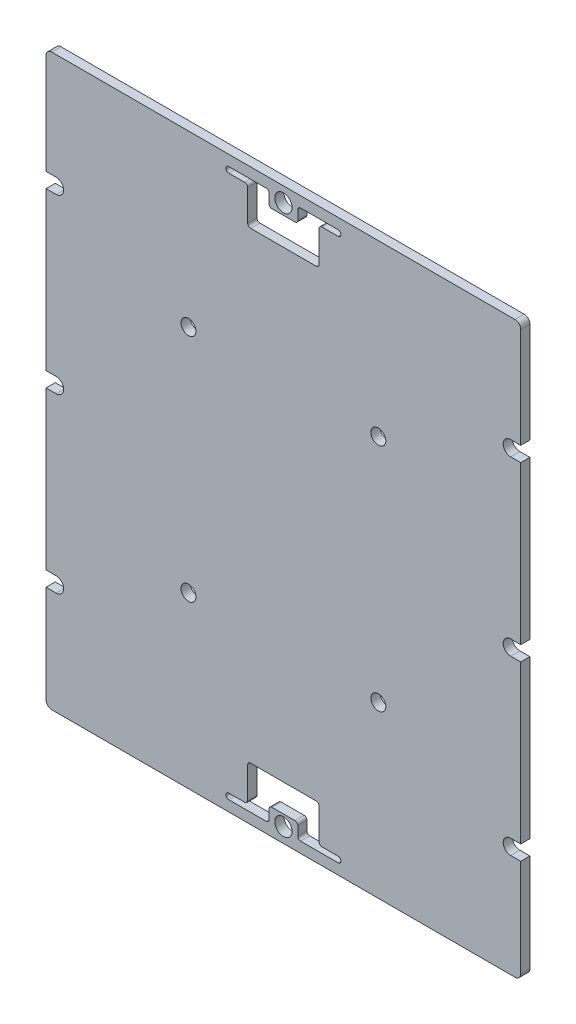
SolidWorks part; units mm, degrees
material "FR4_stuffedProtoboard"
ref_plane "Front Plane" through (0, 0, 0) normal (0, 0, 1) x (1, 0, 0)
ref_plane "Top Plane" through (0, 0, 0) normal (0, 1, 0) x (1, 0, 0)
ref_plane "Right Plane" through (0, 0, 0) normal (1, 0, 0) x (0, 0, -1)
sketch "Sketch2" plane through (0, 0, 0) normal (0, 0, 1) x (1, 0, 0)
  line L0 (39, 49.75) -> (-39, 49.75) construction
  line L1 (-41.5, 49.75) -> (41.5, 49.75) construction
  line L2 (-41.5, 49.75) -> (-41.5, -49.75) construction
  line L3 (-41.5, -49.75) -> (41.5, -49.75) construction
  line L4 (41.5, 49.75) -> (41.5, -49.75) construction
  line L5 (-41.5, 49.75) -> (41.5, -49.75) construction
  line L6 (-41.5, -49.75) -> (41.5, 49.75) construction
  line L7 (41.5, 52.25) -> (41.5, 40.15) construction
  line L8 (-41.5, 49.75) -> (41.5, 49.75) construction
  line L9 (41.5, 49.75) -> (41.5, -49.75) construction
  line L10 (-41.5, -49.75) -> (41.5, -49.75) construction
  line L11 (-41.5, 49.75) -> (-41.5, -49.75) construction
  line L12 (-37, -31.85) -> (37, -31.85) construction
  line L13 (-37, -30.25) -> (37, -30.25) construction
  line L14 (-37, -21.85) -> (37, -21.85) construction
  line L15 (-37, -20.25) -> (37, -20.25) construction
  line L16 (-37, -11.85) -> (37, -11.85) construction
  line L17 (-37, -10.25) -> (37, -10.25) construction
  line L18 (-37, -1.85) -> (37, -1.85) construction
  line L19 (-37, -0.25) -> (37, -0.25) construction
  line L20 (-37, 8.15) -> (37, 8.15) construction
  line L21 (-37, 9.75) -> (37, 9.75) construction
  line L22 (-37, 18.15) -> (37, 18.15) construction
  line L23 (-37, 19.75) -> (37, 19.75) construction
  line L24 (-37, 28.15) -> (37, 28.15) construction
  line L25 (-37, 29.75) -> (37, 29.75) construction
  line L26 (-37, 38.15) -> (37, 38.15) construction
  line L27 (-37, 39.75) -> (37, 39.75) construction
  line L28 (-37, -31.85) -> (37, -31.85) construction
  line L29 (-37, -30.25) -> (37, -30.25) construction
  line L30 (-37, -21.85) -> (37, -21.85) construction
  line L31 (-37, -20.25) -> (37, -20.25) construction
  line L32 (-37, -11.85) -> (37, -11.85) construction
  line L33 (-37, -10.25) -> (37, -10.25) construction
  line L34 (-37, -1.85) -> (37, -1.85) construction
  line L35 (-37, -0.25) -> (37, -0.25) construction
  line L36 (-37, 8.15) -> (37, 8.15) construction
  line L37 (-37, 9.75) -> (37, 9.75) construction
  line L38 (-37, 18.15) -> (37, 18.15) construction
  line L39 (-37, 19.75) -> (37, 19.75) construction
  line L40 (-37, 28.15) -> (37, 28.15) construction
  line L41 (-37, 29.75) -> (37, 29.75) construction
  line L42 (-37, 38.15) -> (37, 38.15) construction
  line L43 (-37, 39.75) -> (37, 39.75) construction
  line L44 (-37, -40.25) -> (37, -40.25) construction
  line L45 (-37, -41.85) -> (37, -41.85) construction
  line L46 (-41.5, 52.25) -> (-41.5, 40.15) construction
  line L47 (39, -49.75) -> (-39, -49.75) construction
  line L48 (41.5, -31.7) -> (41.5, -52.25) construction
  line L49 (-41.25, 49.5) -> (41.25, 49.5)
  line L50 (41.25, 49.5) -> (41.25, -49.5)
  line L51 (-41.25, -49.5) -> (41.25, -49.5)
  line L52 (-41.25, 49.5) -> (-41.25, -49.5)
  circle A0 centre (0, 46.95) radius 1.5 construction
  circle A1 centre (0, 46.95) radius 0.8 construction
  circle A2 centre (0, 46.95) radius 1.5 construction
  circle A3 centre (0, 46.95) radius 0.8
  circle A4 centre (-39.5, -30.25) radius 0.8 construction
  circle A5 centre (-39.5, -0.25) radius 0.8 construction
  circle A6 centre (-39.5, 29.75) radius 0.8 construction
  circle A7 centre (-39.5, -30.25) radius 0.8
  circle A8 centre (-39.5, -0.25) radius 0.8
  circle A9 centre (-39.5, 29.75) radius 0.8
  circle A10 centre (39.5, -30.25) radius 0.8 construction
  circle A11 centre (39.5, -0.25) radius 0.8 construction
  circle A12 centre (39.5, 29.75) radius 0.8 construction
  circle A13 centre (39.5, -30.25) radius 0.8
  circle A14 centre (39.5, -0.25) radius 0.8
  circle A15 centre (39.5, 29.75) radius 0.8
  circle A16 centre (0, -46.95) radius 0.8 construction
  circle A17 centre (0, -46.95) radius 0.8
  circle A18 centre (0, -46.95) radius 1.5 construction
  circle A19 centre (0, -46.95) radius 1.5
  circle A20 centre (-16.5, 20) radius 1.75 construction
  circle A21 centre (-16.5, 20) radius 0.8 construction
  circle A22 centre (-16.5, 20) radius 1.75 construction
  circle A23 centre (-16.5, 20) radius 0.8
  circle A24 centre (16.5, 20) radius 1.75 construction
  circle A25 centre (16.5, 20) radius 0.8 construction
  circle A26 centre (16.5, 20) radius 1.75 construction
  circle A27 centre (16.5, 20) radius 0.8
  circle A28 centre (16.5, -20) radius 1.75 construction
  circle A29 centre (-16.5, -20) radius 1.75 construction
  circle A30 centre (16.5, -20) radius 1.75 construction
  circle A31 centre (-16.5, -20) radius 1.75 construction
  circle A32 centre (-16.5, -20) radius 0.8 construction
  circle A33 centre (-16.5, -20) radius 0.8
  circle A34 centre (16.5, -20) radius 0.8 construction
  circle A35 centre (16.5, -20) radius 0.8
  point P0 (0, 0)
  point P74 (0, -40.25)
  point P75 (0, -31.85)
  point P76 (0, -41.85)
  dimension "D2" = 10
  dimension "D3" = 1.6
  dimension "D1" = 0.25
extrude "pcb extrude" add sketch "Sketch2" along normal mid plane 1.6 contours L4 L1 L2 L3 A2 | A2 A3 | L2 L1 L4 L3 region at (0, 0.0296, 0)
sketch "connector locations" plane through (0, 0, 0.8) normal (0, 0, 1) x (1, 0, 0)
  line L0 (34.5, 45.75) -> (4.5, 45.75) construction
  line L1 (-2.5, 44.75) -> (2.5, 44.75) construction
  line L2 (-4.5, 45.75) -> (-34.5, 45.75) construction
  line L3 (34.5, 45.75) -> (4.5, 45.75)
  line L4 (-2.5, 44.75) -> (2.5, 44.75)
  line L5 (-4.5, 45.75) -> (-34.5, 45.75)
  line L6 (-37, 43.25) -> (-37, -43.25) construction
  line L7 (-37, 43.25) -> (-37, -43.25)
  line L8 (37, -43.25) -> (37, 43.25) construction
  line L9 (37, -43.25) -> (37, 43.25)
  line L10 (4.5, -45.75) -> (34.5, -45.75) construction
  line L11 (4.5, -45.75) -> (34.5, -45.75)
  line L12 (-34.5, -45.75) -> (-4.5, -45.75) construction
  line L13 (-2.5, -44.75) -> (2.5, -44.75) construction
  line L14 (-34.5, -45.75) -> (-4.5, -45.75)
  line L15 (-2.5, -44.75) -> (2.5, -44.75)
  line L16 (-37, 39.75) -> (37, 39.75) construction
  line L17 (-33.9182, 41.909) -> (-9.2802, 41.909)
  line L18 (-33.9182, 41.909) -> (-33.9182, 43.306)
  line L19 (-33.9182, 43.306) -> (-9.2802, 43.306)
  line L20 (-9.2802, 41.909) -> (-9.2802, 43.306)
  line L21 (-33.9182, 41.909) -> (-9.2802, 43.306) construction
  line L22 (-33.9182, 43.306) -> (-9.2802, 41.909) construction
  line L23 (-33.9182, 33.306) -> (-22.0818, 33.306)
  line L24 (-33.9182, 33.306) -> (-33.9182, 31.909)
  line L25 (-33.9182, 31.909) -> (-22.0818, 31.909)
  line L26 (-22.0818, 33.306) -> (-22.0818, 31.909)
  line L27 (-33.9182, 33.306) -> (-22.0818, 31.909) construction
  line L28 (-33.9182, 31.909) -> (-22.0818, 33.306) construction
  line L29 (-12.319, 33.306) -> (12.319, 33.306)
  line L30 (-12.319, 33.306) -> (-12.319, 31.909)
  line L31 (-12.319, 31.909) -> (12.319, 31.909)
  line L32 (12.319, 33.306) -> (12.319, 31.909)
  line L33 (-12.319, 33.306) -> (12.319, 31.909) construction
  line L34 (-12.319, 31.909) -> (12.319, 33.306) construction
  line L35 (-33.9182, 23.306) -> (-22.0818, 23.306)
  line L36 (-33.9182, 23.306) -> (-33.9182, 21.909)
  line L37 (-33.9182, 21.909) -> (-22.0818, 21.909)
  line L38 (-33.9182, 23.306) -> (-22.0818, 21.909) construction
  line L39 (-33.9182, 21.909) -> (-22.0818, 23.306) construction
  line L40 (-22.0818, 23.306) -> (-22.0818, 21.909)
  line L41 (-12.319, 23.306) -> (-12.319, 21.909)
  line L42 (-12.319, 23.306) -> (12.319, 23.306)
  line L43 (-12.319, 21.909) -> (12.319, 21.909)
  line L44 (-12.319, 23.306) -> (12.319, 21.909) construction
  line L45 (-12.319, 21.909) -> (12.319, 23.306) construction
  line L46 (12.319, 23.306) -> (12.319, 21.909)
  line L47 (-33.9182, 13.306) -> (-22.0818, 13.306)
  line L48 (-33.9182, 13.306) -> (-33.9182, 11.909)
  line L49 (-33.9182, 11.909) -> (-22.0818, 11.909)
  line L50 (-33.9182, 13.306) -> (-22.0818, 11.909) construction
  line L51 (-33.9182, 11.909) -> (-22.0818, 13.306) construction
  line L52 (-22.0818, 13.306) -> (-22.0818, 11.909)
  line L53 (-12.319, 13.306) -> (-12.319, 11.909)
  line L54 (-12.319, 13.306) -> (12.319, 13.306)
  line L55 (-12.319, 11.909) -> (12.319, 11.909)
  line L56 (-12.319, 13.306) -> (12.319, 11.909) construction
  line L57 (-12.319, 11.909) -> (12.319, 13.306) construction
  line L58 (12.319, 13.306) -> (12.319, 11.909)
  line L59 (-33.9182, 3.306) -> (-22.0818, 3.306)
  line L60 (-33.9182, 3.306) -> (-33.9182, 1.909)
  line L61 (-33.9182, 1.909) -> (-22.0818, 1.909)
  line L62 (-33.9182, 3.306) -> (-22.0818, 1.909) construction
  line L63 (-33.9182, 1.909) -> (-22.0818, 3.306) construction
  line L64 (-22.0818, 3.306) -> (-22.0818, 1.909)
  line L65 (-12.319, 3.306) -> (-12.319, 1.909)
  line L66 (-12.319, 3.306) -> (12.319, 3.306)
  line L67 (-12.319, 1.909) -> (12.319, 1.909)
  line L68 (-12.319, 3.306) -> (12.319, 1.909) construction
  line L69 (-12.319, 1.909) -> (12.319, 3.306) construction
  line L70 (12.319, 3.306) -> (12.319, 1.909)
  line L71 (-33.9182, -6.694) -> (-22.0818, -6.694)
  line L72 (-33.9182, -6.694) -> (-33.9182, -8.091)
  line L73 (-33.9182, -8.091) -> (-22.0818, -8.091)
  line L74 (-33.9182, -6.694) -> (-22.0818, -8.091) construction
  line L75 (-33.9182, -8.091) -> (-22.0818, -6.694) construction
  line L76 (-22.0818, -6.694) -> (-22.0818, -8.091)
  line L77 (-12.319, -6.694) -> (-12.319, -8.091)
  line L78 (-12.319, -6.694) -> (12.319, -6.694)
  line L79 (-12.319, -8.091) -> (12.319, -8.091)
  line L80 (-12.319, -6.694) -> (12.319, -8.091) construction
  line L81 (-12.319, -8.091) -> (12.319, -6.694) construction
  line L82 (12.319, -6.694) -> (12.319, -8.091)
  line L83 (-33.9182, -16.694) -> (-22.0818, -16.694)
  line L84 (-33.9182, -16.694) -> (-33.9182, -18.091)
  line L85 (-33.9182, -18.091) -> (-22.0818, -18.091)
  line L86 (-33.9182, -16.694) -> (-22.0818, -18.091) construction
  line L87 (-33.9182, -18.091) -> (-22.0818, -16.694) construction
  line L88 (-22.0818, -16.694) -> (-22.0818, -18.091)
  line L89 (-12.319, -16.694) -> (-12.319, -18.091)
  line L90 (-12.319, -16.694) -> (12.319, -16.694)
  line L91 (-12.319, -18.091) -> (12.319, -18.091)
  line L92 (-12.319, -16.694) -> (12.319, -18.091) construction
  line L93 (-12.319, -18.091) -> (12.319, -16.694) construction
  line L94 (12.319, -16.694) -> (12.319, -18.091)
  line L95 (-33.9182, -26.694) -> (-22.0818, -26.694)
  line L96 (-33.9182, -26.694) -> (-33.9182, -28.091)
  line L97 (-33.9182, -28.091) -> (-22.0818, -28.091)
  line L98 (-33.9182, -26.694) -> (-22.0818, -28.091) construction
  line L99 (-33.9182, -28.091) -> (-22.0818, -26.694) construction
  line L100 (-22.0818, -26.694) -> (-22.0818, -28.091)
  line L101 (-12.319, -26.694) -> (-12.319, -28.091)
  line L102 (-12.319, -26.694) -> (12.319, -26.694)
  line L103 (-12.319, -28.091) -> (12.319, -28.091)
  line L104 (-12.319, -26.694) -> (12.319, -28.091) construction
  line L105 (-12.319, -28.091) -> (12.319, -26.694) construction
  line L106 (12.319, -26.694) -> (12.319, -28.091)
  line L107 (-33.9182, -36.694) -> (-22.0818, -36.694)
  line L108 (-33.9182, -36.694) -> (-33.9182, -38.091)
  line L109 (-33.9182, -38.091) -> (-22.0818, -38.091)
  line L110 (-33.9182, -36.694) -> (-22.0818, -38.091) construction
  line L111 (-33.9182, -38.091) -> (-22.0818, -36.694) construction
  line L112 (-22.0818, -36.694) -> (-22.0818, -38.091)
  line L113 (-12.319, -36.694) -> (-12.319, -38.091)
  line L114 (-12.319, -36.694) -> (12.319, -36.694)
  line L115 (-12.319, -38.091) -> (12.319, -38.091)
  line L116 (-12.319, -36.694) -> (12.319, -38.091) construction
  line L117 (-12.319, -38.091) -> (12.319, -36.694) construction
  line L118 (12.319, -36.694) -> (12.319, -38.091)
  line L119 (0, 32.6075) -> (0, 22.6075) construction
  line L120 (-37, 29.75) -> (37, 29.75) construction
  line L121 (32.92, 41.02) -> (35.08, 38.84) construction
  line L122 (32.92, 38.84) -> (35.08, 41.02) construction
  line L123 (26.92, 38.84) -> (29.08, 41.02) construction
  line L124 (26.92, 41.02) -> (29.08, 38.84) construction
  line L125 (20.92, 38.84) -> (23.08, 41.02) construction
  line L126 (20.92, 41.02) -> (23.08, 38.84) construction
  line L127 (26.92, 28.84) -> (29.08, 31.02) construction
  line L128 (26.92, 31.02) -> (29.08, 28.84) construction
  line L129 (20.92, 28.84) -> (23.08, 31.02) construction
  line L130 (20.92, 31.02) -> (23.08, 28.84) construction
  line L131 (26.92, 18.84) -> (29.08, 21.02) construction
  line L132 (26.92, 21.02) -> (29.08, 18.84) construction
  line L133 (20.92, 18.84) -> (23.08, 21.02) construction
  line L134 (20.92, 21.02) -> (23.08, 18.84) construction
  line L135 (26.92, 8.84) -> (29.08, 11.02) construction
  line L136 (26.92, 11.02) -> (29.08, 8.84) construction
  line L137 (20.92, 8.84) -> (23.08, 11.02) construction
  line L138 (20.92, 11.02) -> (23.08, 8.84) construction
  line L139 (26.92, -1.16) -> (29.08, 1.02) construction
  line L140 (26.92, 1.02) -> (29.08, -1.16) construction
  line L141 (20.92, -1.16) -> (23.08, 1.02) construction
  line L142 (20.92, 1.02) -> (23.08, -1.16) construction
  line L143 (26.92, -11.16) -> (29.08, -8.98) construction
  line L144 (26.92, -8.98) -> (29.08, -11.16) construction
  line L145 (20.92, -11.16) -> (23.08, -8.98) construction
  line L146 (20.92, -8.98) -> (23.08, -11.16) construction
  line L147 (26.92, -21.16) -> (29.08, -18.98) construction
  line L148 (26.92, -18.98) -> (29.08, -21.16) construction
  line L149 (20.92, -21.16) -> (23.08, -18.98) construction
  line L150 (20.92, -18.98) -> (23.08, -21.16) construction
  line L151 (26.92, -31.16) -> (29.08, -28.98) construction
  line L152 (26.92, -28.98) -> (29.08, -31.16) construction
  line L153 (20.92, -31.16) -> (23.08, -28.98) construction
  line L154 (20.92, -28.98) -> (23.08, -31.16) construction
  line L155 (26.92, -41.16) -> (29.08, -38.98) construction
  line L156 (26.92, -38.98) -> (29.08, -41.16) construction
  line L157 (20.92, -41.16) -> (23.08, -38.98) construction
  line L158 (20.92, -38.98) -> (23.08, -41.16) construction
  line L159 (32.92, 28.84) -> (35.08, 31.02) construction
  line L160 (32.92, 31.02) -> (35.08, 28.84) construction
  line L161 (32.92, 18.84) -> (35.08, 21.02) construction
  line L162 (32.92, 21.02) -> (35.08, 18.84) construction
  line L163 (32.92, 8.84) -> (35.08, 11.02) construction
  line L164 (32.92, 11.02) -> (35.08, 8.84) construction
  line L165 (32.92, -1.16) -> (35.08, 1.02) construction
  line L166 (32.92, 1.02) -> (35.08, -1.16) construction
  line L167 (32.92, -11.16) -> (35.08, -8.98) construction
  line L168 (32.92, -8.98) -> (35.08, -11.16) construction
  line L169 (32.92, -21.16) -> (35.08, -18.98) construction
  line L170 (32.92, -18.98) -> (35.08, -21.16) construction
  line L171 (32.92, -31.16) -> (35.08, -28.98) construction
  line L172 (32.92, -28.98) -> (35.08, -31.16) construction
  line L173 (32.92, -41.16) -> (35.08, -38.98) construction
  line L174 (32.92, -38.98) -> (35.08, -41.16) construction
  line L175 (34, 39.93) -> (28, 39.93) construction
  line L176 (34, 39.93) -> (34, 29.93) construction
  arc A0 (4.5, 45.75) -> (2.5, 44.75) centre (4.5, 43.25) ccw construction
  arc A1 (-2.5, 44.75) -> (-4.5, 45.75) centre (-4.5, 43.25) ccw construction
  arc A2 (-34.5, 45.75) -> (-37, 43.25) centre (-34.5, 43.25) ccw construction
  arc A3 (4.5, 45.75) -> (2.5, 44.75) centre (4.5, 43.25) ccw
  arc A4 (-2.5, 44.75) -> (-4.5, 45.75) centre (-4.5, 43.25) ccw
  arc A5 (-34.5, 45.75) -> (-37, 43.25) centre (-34.5, 43.25) ccw
  arc A6 (37, 43.25) -> (34.5, 45.75) centre (34.5, 43.25) ccw construction
  arc A7 (37, 43.25) -> (34.5, 45.75) centre (34.5, 43.25) ccw
  arc A8 (34.5, -45.75) -> (37, -43.25) centre (34.5, -43.25) ccw construction
  arc A9 (34.5, -45.75) -> (37, -43.25) centre (34.5, -43.25) ccw
  arc A10 (-37, -43.25) -> (-34.5, -45.75) centre (-34.5, -43.25) ccw construction
  arc A11 (-4.5, -45.75) -> (-2.5, -44.75) centre (-4.5, -43.25) ccw construction
  arc A12 (2.5, -44.75) -> (4.5, -45.75) centre (4.5, -43.25) ccw construction
  arc A13 (-37, -43.25) -> (-34.5, -45.75) centre (-34.5, -43.25) ccw
  arc A14 (-4.5, -45.75) -> (-2.5, -44.75) centre (-4.5, -43.25) ccw
  arc A15 (2.5, -44.75) -> (4.5, -45.75) centre (4.5, -43.25) ccw
  circle A16 centre (-21.5992, 42.6075) radius 0.5
  circle A17 centre (0, 32.6075) radius 0.5
  circle A18 centre (-28, 32.6075) radius 0.5
  circle A19 centre (-28, 22.6075) radius 0.5
  circle A20 centre (0, 22.6075) radius 0.5
  circle A21 centre (-28, 12.6075) radius 0.5
  circle A22 centre (0, 12.6075) radius 0.5
  circle A23 centre (-28, 2.6075) radius 0.5
  circle A24 centre (0, 2.6075) radius 0.5
  circle A25 centre (-28, -7.3925) radius 0.5
  circle A26 centre (0, -7.3925) radius 0.5
  circle A27 centre (-28, -17.3925) radius 0.5
  circle A28 centre (0, -17.3925) radius 0.5
  circle A29 centre (-28, -27.3925) radius 0.5
  circle A30 centre (0, -27.3925) radius 0.5
  circle A31 centre (-28, -37.3925) radius 0.5
  circle A32 centre (0, -37.3925) radius 0.5
  circle A33 centre (35.08, 41.02) radius 0.32
  circle A34 centre (32.92, 38.84) radius 0.32
  circle A35 centre (35.08, 38.84) radius 0.32
  circle A36 centre (32.92, 41.02) radius 0.32
  circle A37 centre (26.92, 41.02) radius 0.32
  circle A38 centre (29.08, 41.02) radius 0.32
  circle A39 centre (26.92, 38.84) radius 0.32
  circle A40 centre (29.08, 38.84) radius 0.32
  circle A41 centre (20.92, 41.02) radius 0.32
  circle A42 centre (23.08, 41.02) radius 0.32
  circle A43 centre (20.92, 38.84) radius 0.32
  circle A44 centre (23.08, 38.84) radius 0.32
  circle A45 centre (26.92, 31.02) radius 0.32
  circle A46 centre (29.08, 31.02) radius 0.32
  circle A47 centre (26.92, 28.84) radius 0.32
  circle A48 centre (29.08, 28.84) radius 0.32
  circle A49 centre (20.92, 31.02) radius 0.32
  circle A50 centre (23.08, 31.02) radius 0.32
  circle A51 centre (20.92, 28.84) radius 0.32
  circle A52 centre (23.08, 28.84) radius 0.32
  circle A53 centre (26.92, 21.02) radius 0.32
  circle A54 centre (29.08, 21.02) radius 0.32
  circle A55 centre (26.92, 18.84) radius 0.32
  circle A56 centre (29.08, 18.84) radius 0.32
  circle A57 centre (20.92, 21.02) radius 0.32
  circle A58 centre (23.08, 21.02) radius 0.32
  circle A59 centre (20.92, 18.84) radius 0.32
  circle A60 centre (23.08, 18.84) radius 0.32
  circle A61 centre (26.92, 11.02) radius 0.32
  circle A62 centre (29.08, 11.02) radius 0.32
  circle A63 centre (26.92, 8.84) radius 0.32
  circle A64 centre (29.08, 8.84) radius 0.32
  circle A65 centre (20.92, 11.02) radius 0.32
  circle A66 centre (23.08, 11.02) radius 0.32
  circle A67 centre (20.92, 8.84) radius 0.32
  circle A68 centre (23.08, 8.84) radius 0.32
  circle A69 centre (26.92, 1.02) radius 0.32
  circle A70 centre (29.08, 1.02) radius 0.32
  circle A71 centre (26.92, -1.16) radius 0.32
  circle A72 centre (29.08, -1.16) radius 0.32
  circle A73 centre (20.92, 1.02) radius 0.32
  circle A74 centre (23.08, 1.02) radius 0.32
  circle A75 centre (20.92, -1.16) radius 0.32
  circle A76 centre (23.08, -1.16) radius 0.32
  circle A77 centre (26.92, -8.98) radius 0.32
  circle A78 centre (29.08, -8.98) radius 0.32
  circle A79 centre (26.92, -11.16) radius 0.32
  circle A80 centre (29.08, -11.16) radius 0.32
  circle A81 centre (20.92, -8.98) radius 0.32
  circle A82 centre (23.08, -8.98) radius 0.32
  circle A83 centre (20.92, -11.16) radius 0.32
  circle A84 centre (23.08, -11.16) radius 0.32
  circle A85 centre (26.92, -18.98) radius 0.32
  circle A86 centre (29.08, -18.98) radius 0.32
  circle A87 centre (26.92, -21.16) radius 0.32
  circle A88 centre (29.08, -21.16) radius 0.32
  circle A89 centre (20.92, -18.98) radius 0.32
  circle A90 centre (23.08, -18.98) radius 0.32
  circle A91 centre (20.92, -21.16) radius 0.32
  circle A92 centre (23.08, -21.16) radius 0.32
  circle A93 centre (26.92, -28.98) radius 0.32
  circle A94 centre (29.08, -28.98) radius 0.32
  circle A95 centre (26.92, -31.16) radius 0.32
  circle A96 centre (29.08, -31.16) radius 0.32
  circle A97 centre (20.92, -28.98) radius 0.32
  circle A98 centre (23.08, -28.98) radius 0.32
  circle A99 centre (20.92, -31.16) radius 0.32
  circle A100 centre (23.08, -31.16) radius 0.32
  circle A101 centre (26.92, -38.98) radius 0.32
  circle A102 centre (29.08, -38.98) radius 0.32
  circle A103 centre (26.92, -41.16) radius 0.32
  circle A104 centre (29.08, -41.16) radius 0.32
  circle A105 centre (20.92, -38.98) radius 0.32
  circle A106 centre (23.08, -38.98) radius 0.32
  circle A107 centre (20.92, -41.16) radius 0.32
  circle A108 centre (23.08, -41.16) radius 0.32
  circle A109 centre (32.92, 31.02) radius 0.32
  circle A110 centre (35.08, 31.02) radius 0.32
  circle A111 centre (32.92, 28.84) radius 0.32
  circle A112 centre (35.08, 28.84) radius 0.32
  circle A113 centre (32.92, 21.02) radius 0.32
  circle A114 centre (35.08, 21.02) radius 0.32
  circle A115 centre (32.92, 18.84) radius 0.32
  circle A116 centre (35.08, 18.84) radius 0.32
  circle A117 centre (32.92, 11.02) radius 0.32
  circle A118 centre (35.08, 11.02) radius 0.32
  circle A119 centre (32.92, 8.84) radius 0.32
  circle A120 centre (35.08, 8.84) radius 0.32
  circle A121 centre (32.92, 1.02) radius 0.32
  circle A122 centre (35.08, 1.02) radius 0.32
  circle A123 centre (32.92, -1.16) radius 0.32
  circle A124 centre (35.08, -1.16) radius 0.32
  circle A125 centre (32.92, -8.98) radius 0.32
  circle A126 centre (35.08, -8.98) radius 0.32
  circle A127 centre (32.92, -11.16) radius 0.32
  circle A128 centre (35.08, -11.16) radius 0.32
  circle A129 centre (32.92, -18.98) radius 0.32
  circle A130 centre (35.08, -18.98) radius 0.32
  circle A131 centre (32.92, -21.16) radius 0.32
  circle A132 centre (35.08, -21.16) radius 0.32
  circle A133 centre (32.92, -28.98) radius 0.32
  circle A134 centre (35.08, -28.98) radius 0.32
  circle A135 centre (32.92, -31.16) radius 0.32
  circle A136 centre (35.08, -31.16) radius 0.32
  circle A137 centre (32.92, -38.98) radius 0.32
  circle A138 centre (35.08, -38.98) radius 0.32
  circle A139 centre (32.92, -41.16) radius 0.32
  circle A140 centre (35.08, -41.16) radius 0.32
  point P18 (-21.5992, 42.6075)
  point P29 (-28, 32.6075)
  point P34 (0, 32.6075)
  point P50 (-28, 22.6075)
  point P55 (0, 22.6075)
  point P64 (-28, 12.6075)
  point P69 (0, 12.6075)
  point P78 (-28, 2.6075)
  point P83 (0, 2.6075)
  point P92 (-28, -7.3925)
  point P97 (0, -7.3925)
  point P106 (-28, -17.3925)
  point P111 (0, -17.3925)
  point P120 (-28, -27.3925)
  point P125 (0, -27.3925)
  point P134 (-28, -37.3925)
  point P139 (0, -37.3925)
  point P158 (0, 0)
  point P165 (34, 39.93)
  point P170 (28, 39.93)
  point P179 (22, 39.93)
  point P188 (28, 29.93)
  point P197 (22, 29.93)
  point P206 (28, 19.93)
  point P215 (22, 19.93)
  point P224 (28, 9.93)
  point P233 (22, 9.93)
  point P242 (28, -0.07)
  point P251 (22, -0.07)
  point P260 (28, -10.07)
  point P269 (22, -10.07)
  point P278 (28, -20.07)
  point P287 (22, -20.07)
  point P296 (28, -30.07)
  point P305 (22, -30.07)
  point P314 (28, -40.07)
  point P323 (22, -40.07)
  point P332 (34, 29.93)
  point P341 (34, 19.93)
  point P350 (34, 9.93)
  point P359 (34, -0.07)
  point P368 (34, -10.07)
  point P377 (34, -20.07)
  point P386 (34, -30.07)
  point P395 (34, -40.07)
  dimension "D4" = 1
  dimension "D5" = 11.8364
  dimension "D10" = 0.64
  dimension "D1" = 24.638
  dimension "D2" = 1.397
  dimension "D3" = 2.159
  dimension "D6" = 28
  dimension "D8" = 10
  dimension "D9" = 2.159
  dimension "D11" = 2.18
  dimension "D12" = 2.16
  dimension "D13" = 0.18
  dimension "D14" = 34
  dimension "D17" = 6
  dimension "D18" = 10
  dimension "D7" = 8
  dimension "D15" = 3
  dimension "D16" = 9
fillet "corner fillets" radius 1 4 edges at (41.25, -49.5, 0) (-41.25, -49.5, 0) (41.25, 49.5, 0) (-41.25, 49.5, 0)
sketch "Sketch4" plane through (0, 0, 0.8) normal (0, 0, 1) x (1, 0, 0)
  line L0 (0, 46.95) -> (0, 40.25) construction
  line L1 (6.2, 40.25) -> (-6.2, 40.25)
  line L2 (-6.2, 40.25) -> (-6.2, 46.65)
  line L3 (-6.2, 46.65) -> (-9.5, 46.65)
  line L4 (-4.5, 45.75) -> (-34.5, 45.75) construction
  line L5 (-9.5, 47.65) -> (-2.5, 47.65)
  line L6 (-2.5, 47.65) -> (-2.5, 45.05)
  line L7 (-2.5, 45.05) -> (2.5, 45.05)
  line L8 (2.5, 47.65) -> (2.5, 45.05)
  line L9 (6.2, 40.25) -> (6.2, 46.65)
  line L10 (6.2, 46.65) -> (9.5, 46.65)
  line L11 (9.5, 47.65) -> (2.5, 47.65)
  line L12 (55, 0) -> (-55, 0) construction
  line L13 (0, -46.95) -> (0, -40.25) construction
  line L14 (9.5, -47.65) -> (2.5, -47.65)
  line L15 (6.2, -46.65) -> (9.5, -46.65)
  line L16 (6.2, -40.25) -> (6.2, -46.65)
  line L17 (2.5, -47.65) -> (2.5, -45.05)
  line L18 (-2.5, -45.05) -> (2.5, -45.05)
  line L19 (-2.5, -47.65) -> (-2.5, -45.05)
  line L20 (-9.5, -47.65) -> (-2.5, -47.65)
  line L21 (-6.2, -46.65) -> (-9.5, -46.65)
  line L22 (-6.2, -40.25) -> (-6.2, -46.65)
  line L23 (6.2, -40.25) -> (-6.2, -40.25)
  arc A0 (-9.5, 47.65) -> (-9.5, 46.65) centre (-9.5, 47.15) ccw
  arc A1 (9.5, 47.65) -> (9.5, 46.65) centre (9.5, 47.15) cw
  circle A2 centre (0, 46.95) radius 1.5
  circle A3 centre (0, -46.95) radius 1.5
  arc A4 (9.5, -47.65) -> (9.5, -46.65) centre (9.5, -47.15) ccw
  arc A5 (-9.5, -47.65) -> (-9.5, -46.65) centre (-9.5, -47.15) cw
  point P17 (0, 45.05)
  point P41 (0, -45.05)
  dimension "D3" = 1
  dimension "D8" = 3
  dimension "D1" = 2.5
  dimension "D2" = 7
  dimension "D4" = 0.9
  dimension "D5" = 6.4
  dimension "D6" = 4.8
  dimension "D7" = 3.7
extrude "solar holes" cut sketch "Sketch4" against normal through all
fillet "solar hole fillets" radius 0.5 16 edges at (-6.2, -46.65, 0) (-2.5, -47.65, 0) (2.5, -47.65, 0) (6.2, -46.65, 0) (2.5, -45.05, 0) (-2.5, -45.05, 0) (6.2, -40.25, 0) (-6.2, -40.25, 0) (6.2, 46.65, 0) (2.5, 47.65, 0) (2.5, 45.05, 0) (6.2, 40.25, 0) (-6.2, 40.25, 0) (-6.2, 46.65, 0) (-2.5, 45.05, 0) (-2.5, 47.65, 0)
sketch "m2 locations" plane through (0, 0, 0.8) normal (0, 0, 1) x (1, 0, 0)
  point P0 (-39.5, 29.75)
  point P1 (-39.5, -0.25)
  point P3 (-39.5, -30.25)
  point P5 (-16.5, -20)
  point P7 (-16.5, 20)
  point P9 (16.5, 20)
  point P11 (16.5, -20)
  point P13 (39.5, -30.25)
  point P15 (39.5, -0.25)
  point P17 (39.5, 29.75)
  point P19 (0, 0)
  point P21 (0, 0)
  point P22 (0, 0)
  point P23 (0, 0)
  point P24 (0, 0)
  point P25 (0, 0)
hole_wizard "M2 Clearance Holes" positions "Sketch8" profile "Sketch9" hole size "M2" standard "ANSI Metric" end condition through all
sketch "Sketch8" plane through (0, 0, 0.8) normal (0, 0, 1) x (1, 0, 0)
  point P0 (-39.5, 29.75)
  point P3 (-39.5, -0.25)
  point P6 (-16.5, 20)
  point P9 (16.5, 20)
  point P12 (16.5, -20)
  point P15 (-16.5, -20)
  point P18 (39.5, 29.75)
  point P21 (39.5, -0.25)
  point P24 (39.5, -30.25)
  point P27 (-39.5, -30.25)
sketch "Sketch9" plane through (-39.5, 29.75, 0.8) normal (1, 0, 0) x (0, -1, 0)
  line L0 (0, 0) -> (0, 1.6)
  line L1 (0, 1.6) -> (1.3, 1.6)
  line L2 (1.3, 1.6) -> (1.3, 0)
  line L5 (1.3, 0) -> (0, 0)
  line L11 (0, -6.35) -> (0, 107.95) construction
  dimension "Thru Hole Dia." = 2.6
  dimension "Thru Hole Depth" = 1.6
sketch "Sketch10" plane through (0, 0, 0.8) normal (0, 0, 1) x (1, 0, 0)
  line L0 (-41.25, 48.5) -> (-41.25, -48.5) construction
  line L1 (-39.5, 31.05) -> (-41.25, 31.05)
  line L2 (-39.5, 31.05) -> (-39.5, 28.45)
  line L3 (-39.5, 28.45) -> (-41.25, 28.45)
  line L4 (-41.25, 31.05) -> (-41.25, 28.45)
  line L5 (41.25, 48.5) -> (41.25, -48.5) construction
  line L6 (-39.5, 1.05) -> (-41.25, 1.05)
  line L7 (-39.5, 1.05) -> (-39.5, -1.55)
  line L8 (-39.5, -1.55) -> (-41.25, -1.55)
  line L9 (-41.25, 1.05) -> (-41.25, -1.55)
  line L10 (-39.5, -28.95) -> (-41.25, -28.95)
  line L11 (-39.5, -28.95) -> (-39.5, -31.55)
  line L12 (-39.5, -31.55) -> (-41.25, -31.55)
  line L13 (-41.25, -28.95) -> (-41.25, -31.55)
  line L14 (39.5, -28.95) -> (41.25, -28.95)
  line L15 (39.5, -28.95) -> (39.5, -31.55)
  line L16 (39.5, -31.55) -> (41.25, -31.55)
  line L17 (41.25, -28.95) -> (41.25, -31.55)
  line L19 (39.5, 1.05) -> (41.25, 1.05)
  line L20 (39.5, 1.05) -> (39.5, -1.55)
  line L21 (39.5, -1.55) -> (41.25, -1.55)
  line L22 (41.25, 1.05) -> (41.25, -1.55)
  line L23 (39.5, 31.05) -> (41.25, 31.05)
  line L24 (39.5, 31.05) -> (39.5, 28.45)
  line L25 (39.5, 28.45) -> (41.25, 28.45)
  line L26 (41.25, 31.05) -> (41.25, 28.45)
  circle A0 centre (-39.5, 29.75) radius 1.3 construction
  circle A1 centre (-39.5, -0.25) radius 1.3 construction
  circle A2 centre (-39.5, -30.25) radius 1.3 construction
  circle A3 centre (39.5, -30.25) radius 1.3 construction
  circle A4 centre (39.5, -0.25) radius 1.3 construction
  circle A5 centre (39.5, 29.75) radius 1.3 construction
  point P40 (-39.5, 28.45)
  point P41 (-39.6207, 31.0444)
  point P43 (-39.5, 29.75)
  point P44 (-39.5, -1.5277)
  point P46 (-39.5448, -31.5492)
  point P48 (39.5, -31.55)
  point P50 (39.3124, -1.5364)
  point P52 (39.5897, 28.4531)
extrude "Cut-Extrude2" cut sketch "Sketch10" against normal through all
